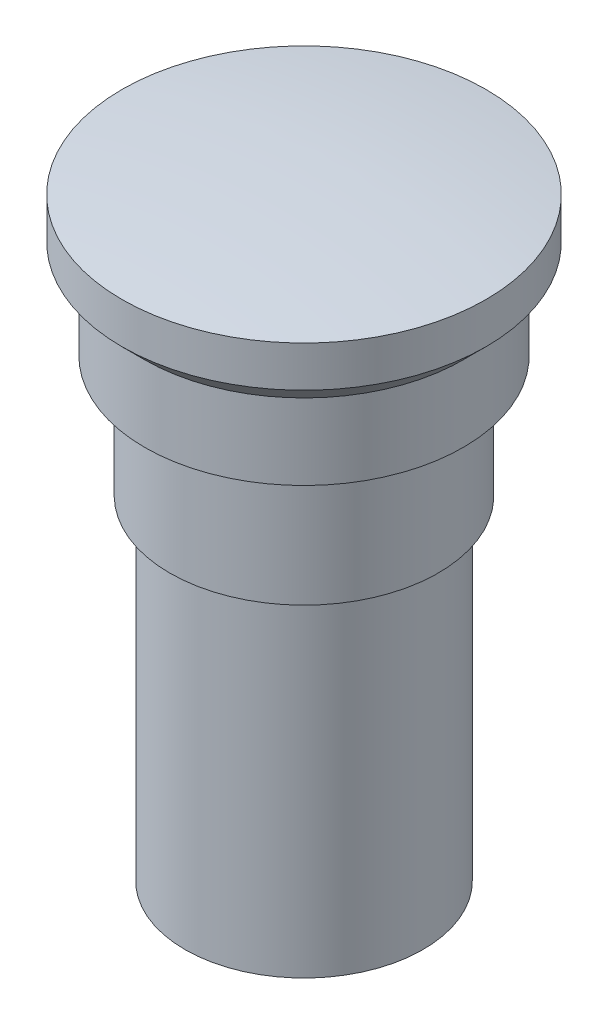
SolidWorks part; units mm, degrees
ref_plane "前视基准面" through (0, 0, 0) normal (0, 0, 1) x (1, 0, 0)
ref_plane "上视基准面" through (0, 0, 0) normal (0, 1, 0) x (1, 0, 0)
ref_plane "右视基准面" through (0, 0, 0) normal (1, 0, 0) x (0, 0, -1)
sketch "草图1" plane through (0, 0, 0) normal (0, 0, 1) x (1, 0, 0)
  line L0 (0, 0) -> (-7.85, 0)
  line L1 (-7.85, 0) -> (-7.85, 22)
  line L2 (-7.85, 22) -> (-8.85, 22)
  line L3 (-8.85, 22) -> (-8.85, 30)
  line L4 (-8.85, 30) -> (-10.5, 30)
  line L5 (-10.5, 30) -> (-10.5, 35)
  line L6 (-10.5, 35) -> (-12, 35)
  line L7 (-12, 35) -> (-12, 40) construction
  line L8 (-12, 40) -> (0, 40) construction
  line L9 (0, 40) -> (0, 0)
  line L10 (-12, 35) -> (-12, 39.1964)
  arc A0 (0, 40) -> (-12, 39.1964) centre (0, -50) ccw
  dimension "D9" = 180
  dimension "D1" = 7.85
  dimension "D2" = 22
  dimension "D3" = 8
  dimension "D4" = 5
  dimension "D5" = 5
  dimension "D6" = 8.85
  dimension "D7" = 10.5
  dimension "D8" = 12
revolve "旋转1" add sketch "草图1" angle 360 about L9
chamfer "倒角1" distance 1.5 angle 45 1 edges at (0, 35, 12)
